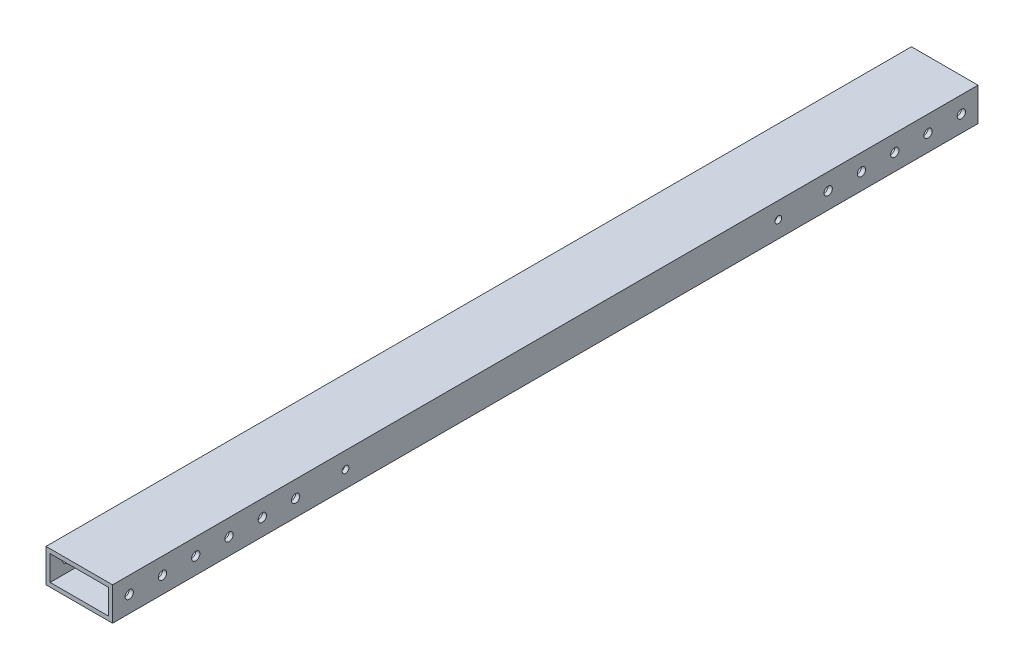
SolidWorks part; units mm, degrees
material "6061 Alloy"
ref_plane "Front Plane" through (0, 0, 0) normal (0, 0, 1) x (1, 0, 0)
ref_plane "Top Plane" through (0, 0, 0) normal (0, 1, 0) x (1, 0, 0)
ref_plane "Right Plane" through (0, 0, 0) normal (1, 0, 0) x (0, 0, -1)
sketch "Sketch1" plane through (0, 0, 0) normal (0, 0, 1) x (1, 0, 0)
  line L0 (-22.225, 9.525) -> (22.225, 9.525)
  line L2 (-25.4, 12.7) -> (25.4, 12.7)
  line L3 (-25.4, 12.7) -> (-25.4, -12.7)
  line L4 (-25.4, -12.7) -> (25.4, -12.7)
  line L5 (25.4, 12.7) -> (25.4, -12.7)
  line L10 (22.225, 9.525) -> (22.225, -9.525)
  line L11 (-22.225, -9.525) -> (22.225, -9.525)
  line L12 (-22.225, 9.525) -> (-22.225, -9.525)
  point P12 (0, 12.7)
  point P14 (25.4, 0)
  dimension "Wall Thickness" = 3.175
  dimension "Outside Width" = 50.8
  dimension "Outside Height" = 25.4
  dimension "Inside Height" = 19.05
  dimension "Inside Width" = 44.45
sketch "Sketch2" plane through (0, 0, 0) normal (1, 0, 0) x (0, 0, -1)
  line L0 (330.2, 0) -> (-330.2, 0)
  point P4 (0, 0)
  point P7 (-330.2, 0)
  point P10 (330.2, 0)
  dimension "Length" = 660.4
sketch "Sketch3" plane through (0, 0, 0) normal (0, 0, 1) x (1, 0, 0)
  line L21 (25.4, 12.7) -> (-25.4, 12.7)
  line L22 (25.4, -12.7) -> (25.4, 12.7)
  line L23 (-25.4, -12.7) -> (25.4, -12.7)
  line L24 (-25.4, 12.7) -> (-25.4, -12.7)
  line L25 (25.4, 12.7) -> (-25.4, 12.7)
  line L26 (25.4, -12.7) -> (25.4, 12.7)
  line L27 (-25.4, -12.7) -> (25.4, -12.7)
  line L28 (-25.4, 12.7) -> (-25.4, -12.7)
  line L29 (22.225, 9.525) -> (-22.225, 9.525)
  line L30 (22.225, -9.525) -> (22.225, 9.525)
  line L31 (-22.225, -9.525) -> (22.225, -9.525)
  line L32 (-22.225, 9.525) -> (-22.225, -9.525)
  line L33 (22.225, 9.525) -> (-22.225, 9.525)
  line L34 (22.225, -9.525) -> (22.225, 9.525)
  line L35 (-22.225, -9.525) -> (22.225, -9.525)
  line L36 (-22.225, 9.525) -> (-22.225, -9.525)
  dimension "D1" = 0
  dimension "D2" = 0
extrude "Boss-Extrude1" add sketch "Sketch3" along normal up to vertex (330.2 mm away) and the other way up to vertex (330.2 mm away) up to point (0, 0, 330.2) other way up to point (0, 0, -330.2)
sketch "Drawing Reference" plane through (0, 0, 0) normal (1, 0, 0) x (0, 0, -1)
  line L0 (-330.2, 0) -> (330.2, 0) construction
  line L1 (0, -12.7) -> (0, 12.7) construction
  line L2 (-330.2, -12.7) -> (330.2, -12.7) construction
  line L5 (-330.2, 12.7) -> (330.2, 12.7) construction
  point P7 (-293.624, 0)
  point P8 (293.624, 0)
  dimension "D1" = 36.576
sketch "Sketch5" plane through (25.4, 0, 0) normal (1, 0, 0) x (0, 0, -1)
  line L2 (-266.7, 0) -> (-241.3, 0)
  line L3 (-241.3, 0) -> (-215.9, 0)
  line L4 (-215.9, 0) -> (-190.5, 0)
  line L5 (-317.5, 0) -> (-330.2, 0)
  line L6 (-330.2, -12.7) -> (-330.2, 12.7) construction
  line L7 (-317.5, 0) -> (-292.1, 0)
  line L8 (-292.1, 0) -> (-266.7, 0)
sketch "Sketch8" plane through (25.4, 0, 0) normal (1, 0, 0) x (0, 0, -1)
  line L0 (330.2, 0) -> (292.1, 0)
  line L1 (330.2, -12.7) -> (330.2, 12.7) construction
  line L2 (292.1, 0) -> (266.7, 0)
  line L3 (266.7, 0) -> (241.3, 0)
  line L4 (241.3, 0) -> (215.9, 0)
  line L5 (330.2, 0) -> (317.5, 0)
hole_wizard "1/4 (0.25) Diameter Hole3" positions "Sketch12" profile "Sketch13" hole size "1/4" standard "ANSI Inch" end condition through all
sketch "Sketch12" plane through (-25.4, 0, 0) normal (-1, 0, 0) x (0, 0, 1)
  point P4 (-317.5, 0)
sketch "Sketch13" plane through (-25.4, 0, -317.5) normal (0, 1, 0) x (0, 0, 1)
  line L0 (0, 0) -> (0, 50.8)
  line L1 (0, 50.8) -> (3.175, 50.8)
  line L2 (3.175, 50.8) -> (3.175, 0)
  line L5 (3.175, 0) -> (0, 0)
  line L11 (0, -6.35) -> (0, 107.95) construction
  dimension "Thru Hole Dia." = 6.35
  dimension "Thru Hole Depth" = 50.8
hole_wizard "1/4 (0.25) Diameter Hole4" positions "Sketch14" profile "Sketch15" hole size "1/4" standard "ANSI Inch" end condition through all
sketch "Sketch14" plane through (-25.4, 0, 0) normal (-1, 0, 0) x (0, 0, 1)
  point P0 (292.1, 0)
  point P3 (317.5, 0)
sketch "Sketch15" plane through (-25.4, 0, 292.1) normal (0, 1, 0) x (0, 0, 1)
  line L0 (0, 0) -> (0, 50.8)
  line L1 (0, 50.8) -> (3.175, 50.8)
  line L2 (3.175, 50.8) -> (3.175, 0)
  line L5 (3.175, 0) -> (0, 0)
  line L11 (0, -6.35) -> (0, 107.95) construction
  dimension "Thru Hole Dia." = 6.35
  dimension "Thru Hole Depth" = 50.8
hole_wizard "1/4 (0.25) Diameter Hole5" positions "Sketch17" profile "Sketch18" hole size "1/4" standard "ANSI Inch" end condition through all
sketch "Sketch17" plane through (25.4, 0, 0) normal (1, 0, 0) x (0, 0, -1)
  point P0 (292.1, 0)
  point P3 (266.7, 0)
sketch "Sketch18" plane through (25.4, 0, -292.1) normal (0, 1, 0) x (0, 0, -1)
  line L0 (0, 0) -> (0, 50.8)
  line L1 (0, 50.8) -> (3.175, 50.8)
  line L2 (3.175, 50.8) -> (3.175, 0)
  line L5 (3.175, 0) -> (0, 0)
  line L11 (0, -6.35) -> (0, 107.95) construction
  dimension "Thru Hole Dia." = 6.35
  dimension "Thru Hole Depth" = 50.8
hole_wizard "1/4 (0.25) Diameter Hole6" positions "Sketch19" profile "Sketch20" hole size "1/4" standard "ANSI Inch" end condition through all
sketch "Sketch19" plane through (25.4, 0, 0) normal (1, 0, 0) x (0, 0, -1)
  point P0 (215.9, 0)
  point P3 (241.3, 0)
sketch "Sketch20" plane through (25.4, 0, -215.9) normal (0, 1, 0) x (0, 0, -1)
  line L0 (0, 0) -> (0, 50.8)
  line L1 (0, 50.8) -> (3.175, 50.8)
  line L2 (3.175, 50.8) -> (3.175, 0)
  line L5 (3.175, 0) -> (0, 0)
  line L11 (0, -6.35) -> (0, 107.95) construction
  dimension "Thru Hole Dia." = 6.35
  dimension "Thru Hole Depth" = 50.8
hole_wizard "1/4 (0.25) Diameter Hole7" positions "Sketch21" profile "Sketch22" hole size "1/4" standard "ANSI Inch" end condition through all
sketch "Sketch21" plane through (25.4, 0, 0) normal (1, 0, 0) x (0, 0, -1)
  point P0 (-190.5, 0)
  point P3 (-215.9, 0)
sketch "Sketch22" plane through (25.4, 0, 190.5) normal (0, 1, 0) x (0, 0, -1)
  line L0 (0, 0) -> (0, 50.8)
  line L1 (0, 50.8) -> (3.175, 50.8)
  line L2 (3.175, 50.8) -> (3.175, 0)
  line L5 (3.175, 0) -> (0, 0)
  line L11 (0, -6.35) -> (0, 107.95) construction
  dimension "Thru Hole Dia." = 6.35
  dimension "Thru Hole Depth" = 50.8
hole_wizard "1/4 (0.25) Diameter Hole8" positions "Sketch23" profile "Sketch24" hole size "1/4" standard "ANSI Inch" end condition through all
sketch "Sketch23" plane through (25.4, 0, 0) normal (1, 0, 0) x (0, 0, -1)
  point P0 (-266.7, 0)
  point P3 (-241.3, 0)
sketch "Sketch24" plane through (25.4, 0, 266.7) normal (0, 1, 0) x (0, 0, -1)
  line L0 (0, 0) -> (0, 50.8)
  line L1 (0, 50.8) -> (3.175, 50.8)
  line L2 (3.175, 50.8) -> (3.175, 0)
  line L5 (3.175, 0) -> (0, 0)
  line L11 (0, -6.35) -> (0, 107.95) construction
  dimension "Thru Hole Dia." = 6.35
  dimension "Thru Hole Depth" = 50.8
sketch "Sketch25" plane through (25.4, 0, 0) normal (1, 0, 0) x (0, 0, -1)
  line L0 (-190.5, 0) -> (-152.4, 0)
  line L1 (215.9, 0) -> (177.8, 0)
hole_wizard "13/64 (0.20313) Diameter Hole1" positions "Sketch26" profile "Sketch27" hole size "13/64" standard "ANSI Inch" end condition through all
sketch "Sketch26" plane through (25.4, 0, 0) normal (1, 0, 0) x (0, 0, -1)
  point P0 (-152.4, 0)
  point P3 (177.8, 0)
sketch "Sketch27" plane through (25.4, 0, 152.4) normal (0, 1, 0) x (0, 0, -1)
  line L0 (0, 0) -> (0, 50.8)
  line L1 (0, 50.8) -> (2.5798, 50.8)
  line L2 (2.5798, 50.8) -> (2.5798, 0)
  line L5 (2.5798, 0) -> (0, 0)
  line L11 (0, -6.35) -> (0, 107.95) construction
  dimension "Thru Hole Dia." = 5.1595
  dimension "Thru Hole Depth" = 50.8
hole_wizard "1/2 (0.5) Diameter Hole1" positions "Sketch33" profile "Sketch34" hole size "1/2" standard "ANSI Inch"
sketch "Sketch33" plane through (-25.4, 0, 0) normal (-1, 0, 0) x (0, 0, 1)
  point P0 (-158.75, 0)
  point P3 (133.35, 0)
  point P8 (-158.75, 0)
  point P10 (133.35, 0)
sketch "Sketch34" plane through (-25.4, 0, -158.75) normal (0, 1, 0) x (0, 0, 1)
  line L0 (0, 0) -> (0, 10.1655)
  line L1 (0, 10.1655) -> (6.35, 6.35)
  line L2 (6.35, 6.35) -> (6.35, 0)
  line L5 (6.35, 0) -> (0, 0)
  line L10 (0, 10.1655) -> (-6.35, 6.35) construction
  line L11 (0, -6.35) -> (0, 107.95) construction
  dimension "Hole Dia." = 12.7
  dimension "Hole Depth" = 6.35
  dimension "Drill Angle" = 118
equation "\"D1@Drawing Reference\"=\"Outside Width@Sketch1\" * 0.72"
